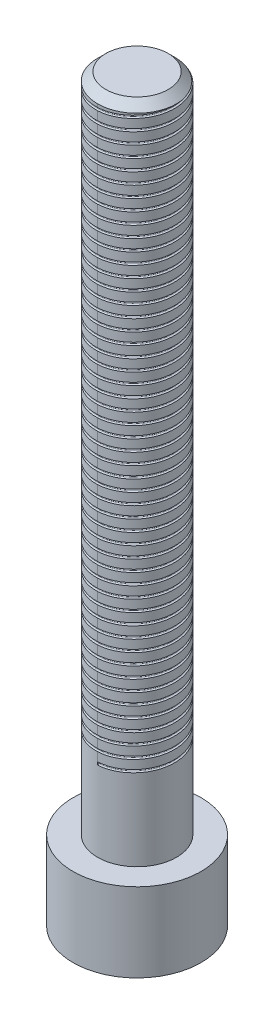
SolidWorks part; units mm, degrees
note: '?' marks a value the reader was unsure of.
ref_plane "Front Plane" through (0, 0, 0) normal (0, 0, 1) x (1, 0, 0)
ref_plane "Top Plane" through (0, 0, 0) normal (0, 1, 0) x (1, 0, 0)
ref_plane "Right Plane" through (0, 0, 0) normal (1, 0, 0) x (0, 0, -1)
sketch "Sketch1" plane through (0, 0, 0) normal (0, 1, 0) x (1, 0, 0)
  line L1 (4.4745, 0) -> (2.2372, 3.875) construction
  line L2 (2.2372, 3.875) -> (-2.2372, 3.875) construction
  line L3 (-2.2372, 3.875) -> (-4.4745, 0) construction
  line L4 (-4.4745, 0) -> (-2.2372, -3.875) construction
  line L5 (-2.2372, -3.875) -> (2.2372, -3.875) construction
  line L6 (2.2372, -3.875) -> (4.4745, 0) construction
  circle A0 centre (0, 0) radius 3.875
  dimension "D1" = 7.75
extrude "Boss-Extrude1" add sketch "Sketch1" along normal blind 44.78
sketch "Sketch2" plane through (0, 44.78, 0) normal (0, 1, 0) x (1, 0, 0)
  circle A0 centre (0, 0) radius 2.39
  dimension "D1" = 4.78
extrude "Cut-Extrude1" cut sketch "Sketch2" against normal blind 40 flip side to cut
ref_axis "Axis1" through (0, 4.78, 0) along (0, 1, 0)?
chamfer "Chamfer1" distance 0.5 angle 45 1 edges at (0, 44.78, 2.39)
sketch "Sketch5" plane through (0, 44.78, 0) normal (0, 1, 0) x (1, 0, 0)
  circle A0 centre (0, 0) radius 2.39
  dimension "D1" = 4.78
curve "Helix/Spiral1" pitch 0.7 height 35 turns 50
ref_plane "Plane1" through (0, 44.78, 2.39) normal (-0.9989, -0.0466, 0) x (0, 0, 1)
sketch "Sketch7" plane through (0, 44.78, 2.39) normal (-0.9989, -0.0466, 0) x (0, 0, 1)
  line L0 (-0.081, -0.0303) -> (0.549, 0.2747)
  line L1 (0.549, 0.2747) -> (0.549, -0.4253)
  line L2 (0.549, -0.4253) -> (-0.081, -0.1203)
  arc A0 (-0.081, -0.0303) -> (-0.081, -0.1203) centre (-0.0592, -0.0753) ccw
  dimension "D2" = 0.05
  dimension "D1" = 0.7
sweep "Cut-Sweep1" cut profiles "Sketch7" path "Helix/Spiral1"
sketch "Sketch8" plane through (0, 0, 0) normal (0, -1, 0) x (1, 0, 0)
  line L1 (2.6443, 0) -> (1.3221, 2.29)
  line L2 (1.3221, 2.29) -> (-1.3221, 2.29)
  line L3 (-1.3221, 2.29) -> (-2.6443, 0)
  line L4 (-2.6443, 0) -> (-1.3221, -2.29)
  line L5 (-1.3221, -2.29) -> (1.3221, -2.29)
  line L6 (1.3221, -2.29) -> (2.6443, 0)
  circle A0 centre (0, 0) radius 2.29 construction
  dimension "D1" = 4.58
extrude "Cut-Extrude2" cut sketch "Sketch8" against normal blind 3.36
